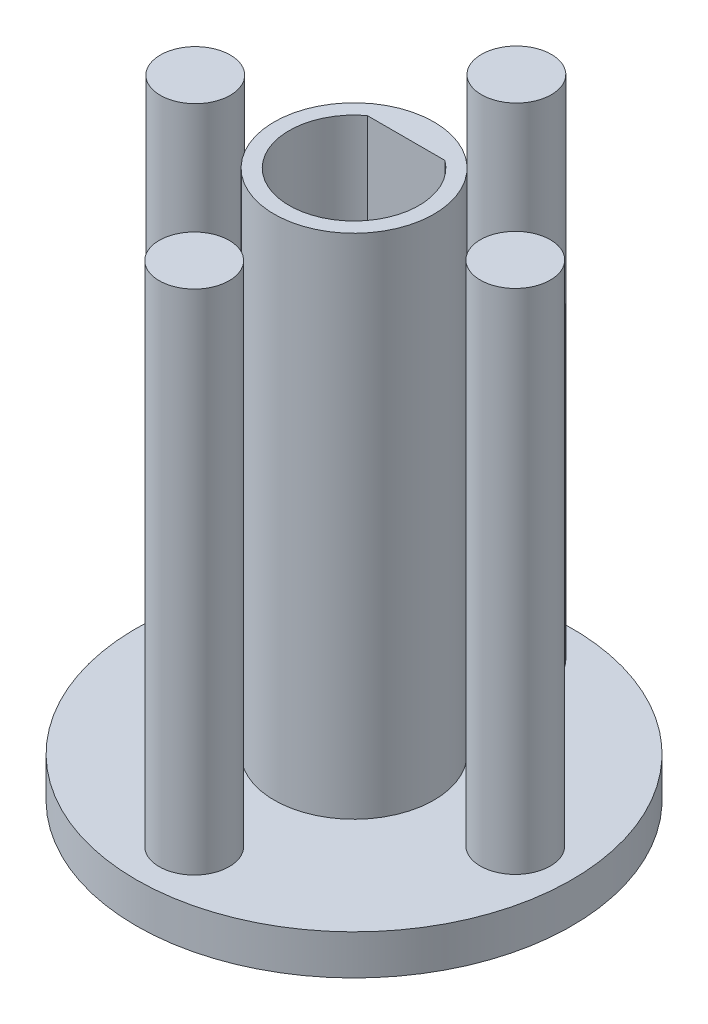
SolidWorks part; units mm, degrees
ref_plane "Front Plane" through (0, 0, 0) normal (0, 0, 1) x (1, 0, 0)
ref_plane "Top Plane" through (0, 0, 0) normal (0, 1, 0) x (1, 0, 0)
ref_plane "Right Plane" through (0, 0, 0) normal (1, 0, 0) x (0, 0, -1)
sketch "Sketch3" plane through (0, 0, 0) normal (0, 1, 0) x (1, 0, 0)
  line L0 (-7.9995, 0.0532) -> (0.009, 8.1156) construction
  line L1 (0.009, 8.1156) -> (8.0177, 0.0533) construction
  line L2 (8.0177, 0.0533) -> (0.0092, -8.0091) construction
  line L3 (0.0092, -8.0091) -> (-7.9995, 0.0532) construction
  line L5 (0.009, -3.25) -> (0.009, 2.6055)
  line L7 (18.7783, 0.0532) -> (-25.5315, 0.0532) construction
  line L8 (9.7482, 0.0532) -> (10.8982, 0.0532)
  line L9 (-1.9426, 2.6055) -> (1.9426, 2.6055)
  line L11 (0.009, -13.1564) -> (0.009, 16.0208) construction
  circle A0 centre (0, 0) radius 10.9
  circle A1 centre (0.009, 8.1156) radius 1.75
  circle A2 centre (8.0177, 0.0533) radius 1.75
  circle A3 centre (0.0092, -8.0091) radius 1.75
  circle A4 centre (-7.9995, 0.0532) radius 1.75
  circle A5 centre (0, 0) radius 4
  arc A6 (-1.9426, 2.6055) -> (1.9426, 2.6055) centre (0, 0) ccw
  dimension "D1" = 21.8
extrude "Boss-Extrude1" add sketch "Sketch3" along normal blind 27.4 contours A3 | A4 | A1 | A2 | A6 L9 | A5
extrude "Boss-Extrude2" add sketch "Sketch3<13>" along normal blind 2 contours A0
sketch "Sketch3<13>" plane through (0, 0, 0) normal (0, 1, 0) x (1, 0, 0) same geometry as "Sketch3"
